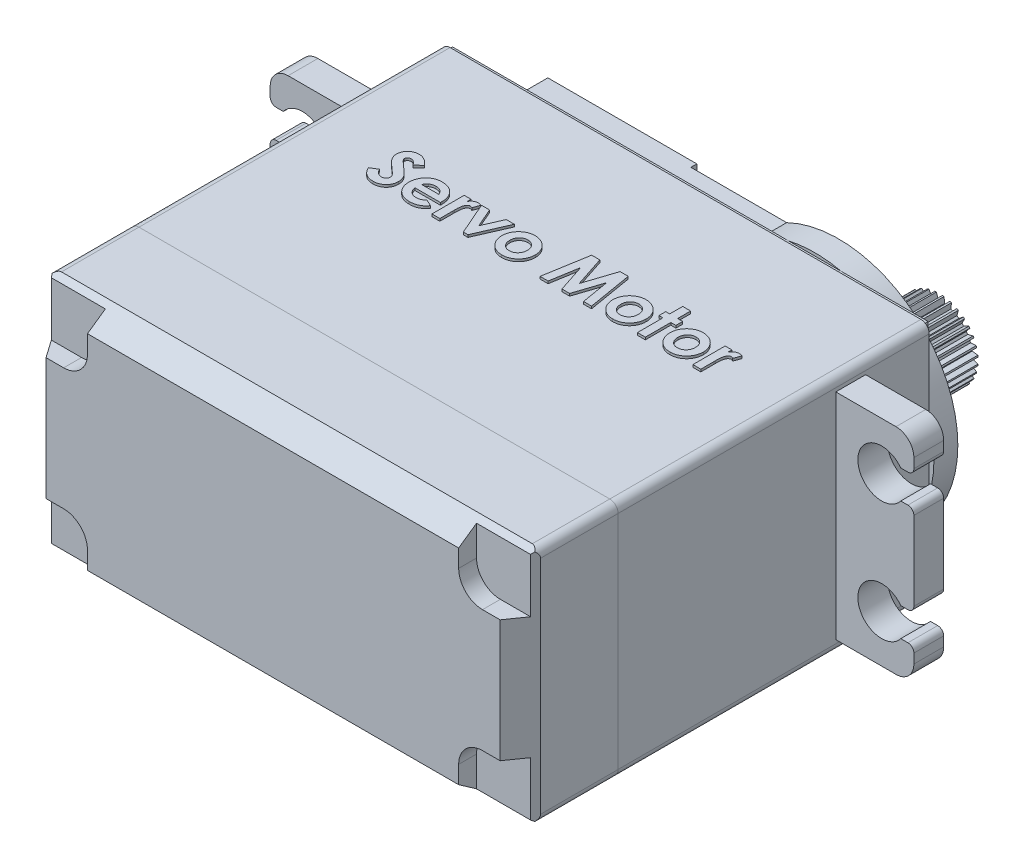
SolidWorks part; units mm, degrees
ref_plane "Front Plane" through (0, 0, 0) normal (0, 0, 1) x (1, 0, 0)
ref_plane "Top Plane" through (0, 0, 0) normal (0, 1, 0) x (1, 0, 0)
ref_plane "Right Plane" through (0, 0, 0) normal (1, 0, 0) x (0, 0, -1)
sketch "Sketch1" plane through (0, 0, 0) normal (0, 0, 1) x (1, 0, 0)
  line L1 (20.45, 10) -> (-20.45, 10)
  line L2 (20.45, 10) -> (20.45, -10)
  line L3 (20.45, -10) -> (-20.45, -10)
  line L4 (-20.45, 10) -> (-20.45, -10)
  line L5 (20.45, 10) -> (-20.45, -10) construction
  line L6 (20.45, -10) -> (-20.45, 10) construction
  point P0 (0, 0)
  dimension "D1" = 20
  dimension "D2" = 40.9
extrude "Boss-Extrude1" add sketch "Sketch1" along normal blind 19.3
sketch "Sketch2" plane through (0, 0, 0) normal (0, 0, -1) x (-1, 0, 0)
  line L4 (20.45, -10) -> (20.45, 10)
  line L5 (20.45, 10) -> (-20.45, 10)
  line L6 (-20.45, 10) -> (-20.45, -10)
  line L7 (-20.45, -10) -> (20.45, -10)
  line L8 (20.45, -10) -> (20.45, 10)
  line L9 (20.45, 10) -> (-20.45, 10)
  line L10 (-20.45, 10) -> (-20.45, -10)
  line L11 (-20.45, -10) -> (20.45, -10)
  dimension "D1" = 0
extrude "Boss-Extrude2" add sketch "Sketch2" along normal blind 6.8 separate body
sketch "Sketch3" plane through (0, 0, 19.3) normal (0, 0, 1) x (1, 0, 0)
  line L4 (-20.45, 10) -> (-20.45, -10)
  line L5 (-20.45, -10) -> (20.45, -10)
  line L6 (20.45, -10) -> (20.45, 10)
  line L7 (20.45, 10) -> (-20.45, 10)
  line L8 (-20.45, 10) -> (-20.45, -10)
  line L9 (-20.45, -10) -> (20.45, -10)
  line L10 (20.45, -10) -> (20.45, 10)
  line L11 (20.45, 10) -> (-20.45, 10)
  dimension "D1" = 0
extrude "Boss-Extrude3" add sketch "Sketch3" along normal blind 8.5 separate body
chamfer "Chamfer1" distance 2 angle 35 4 edges at (20.45, 0, 27.8) (0, -10, 27.8) (-20.45, 0, 27.8) (0, 10, 27.8) first distance on face at (20.45, 0, 23.55) first distance on face at (0, -10, 23.55) first distance on face at (-20.45, 0, 23.55) first distance on face at (0, 10, 23.55)
sketch "Sketch4" plane through (0, 0, 27.8) normal (0, 0, 1) x (1, 0, 0)
  line L0 (0, 0) -> (0, 10) construction
  line L1 (-20.45, 10) -> (-15.57, 10)
  line L2 (-20.45, 10) -> (-20.45, 5.12)
  line L3 (-20.45, 5.12) -> (-17.57, 5.12)
  line L4 (-15.57, 10) -> (-15.57, 7.12)
  line L5 (-20.45, 10) -> (20.45, 10) construction
  line L6 (0, 0) -> (20.45, 0) construction
  line L7 (20.45, 10) -> (20.45, -10) construction
  line L8 (15.57, 10) -> (15.57, 7.12)
  line L9 (20.45, 5.12) -> (17.57, 5.12)
  line L10 (20.45, 10) -> (20.45, 5.12)
  line L11 (20.45, 10) -> (15.57, 10)
  line L12 (-15.57, -10) -> (-15.57, -7.12)
  line L13 (-20.45, -5.12) -> (-17.57, -5.12)
  line L14 (-20.45, -10) -> (-20.45, -5.12)
  line L15 (-20.45, -10) -> (-15.57, -10)
  line L16 (20.45, -10) -> (15.57, -10)
  line L17 (20.45, -10) -> (20.45, -5.12)
  line L18 (20.45, -5.12) -> (17.57, -5.12)
  line L19 (15.57, -10) -> (15.57, -7.12)
  arc A0 (-17.57, 5.12) -> (-15.57, 7.12) centre (-17.57, 7.12) ccw
  arc A1 (17.57, 5.12) -> (15.57, 7.12) centre (17.57, 7.12) cw
  arc A2 (-17.57, -5.12) -> (-15.57, -7.12) centre (-17.57, -7.12) cw
  arc A3 (17.57, -5.12) -> (15.57, -7.12) centre (17.57, -7.12) ccw
  dimension "D3" = 2
  dimension "D1" = 4.88
  dimension "D2" = 4.88
extrude "Cut-Extrude1" cut sketch "Sketch4" against normal blind 1.5
sketch "Sketch5" plane through (0, 0, -6.8) normal (0, 0, -1) x (-1, 0, 0)
  line L1 (19.95, 9.75) -> (-19.95, 9.75)
  line L2 (19.95, 9.75) -> (19.95, -9.75)
  line L3 (19.95, -9.75) -> (-19.95, -9.75)
  line L4 (-19.95, 9.75) -> (-19.95, -9.75)
  line L5 (19.95, 9.75) -> (-19.95, -9.75) construction
  line L6 (19.95, -9.75) -> (-19.95, 9.75) construction
  line L7 (20.45, 10) -> (-20.45, 10) construction
  line L8 (20.45, -10) -> (20.45, 10) construction
  point P0 (0, 0)
  dimension "D1" = 0.25
  dimension "D2" = 0.5
extrude "Boss-Extrude4" add sketch "Sketch5" along normal blind 0.4
sketch "Sketch7" plane through (0, 0, -7.2) normal (0, 0, -1) x (-1, 0, 0)
  line L0 (-20.45, 0) -> (20.45, 0) construction
  line L1 (-20.45, 10) -> (-20.45, -10) construction
  line L2 (20.45, -10) -> (20.45, 10) construction
  line L3 (20.45, 10) -> (-20.45, 10) construction
  line L4 (-6.09, 9.75) -> (-6.09, -9.75) construction
  line L5 (19.95, 9.75) -> (-19.95, 9.75) construction
  line L6 (-19.95, -9.75) -> (19.95, -9.75) construction
  line L7 (-6.09, 8.9995) -> (14.45, 8.9995)
  line L8 (14.45, 8.9995) -> (14.45, 3.9188)
  line L9 (14.45, -8.9995) -> (14.45, -3.9188)
  line L10 (-6.09, -8.9995) -> (14.45, -8.9995)
  arc A0 (-6.09, 8.9995) -> (-6.09, -8.9995) centre (-10.45, 0) ccw
  arc A1 (14.45, -3.9188) -> (14.45, 3.9188) centre (13.3905, 0) ccw
  point P23 (17.45, 0)
  dimension "D1" = 14.36
  dimension "D2" = 6
  dimension "D3" = 3
extrude "Boss-Extrude5" add sketch "Sketch7" along normal blind 2
sketch "Sketch8" plane through (0, 0, -9.2) normal (0, 0, -1) x (-1, 0, 0)
  circle A0 centre (-11.9002, 0) radius 6.5
  dimension "D1" = 13
extrude "Boss-Extrude6" add sketch "Sketch8" along normal blind 1.5
sketch "Sketch9" plane through (0, 0, -10.7) normal (0, 0, -1) x (-1, 0, 0)
  circle A0 centre (-11.9002, 0) radius 5.5
  dimension "D1" = 11
extrude "Boss-Extrude7" add sketch "Sketch9" along normal blind 0.5
sketch "Sketch10" plane through (0, 0, -11.2) normal (0, 0, -1) x (-1, 0, 0)
  circle A0 centre (-11.9002, 0) radius 3.25
  dimension "D1" = 6.5
extrude "Boss-Extrude8" add sketch "Sketch10" along normal blind 5
sketch "Sketch11" plane through (0, 0, -9.2) normal (0, 0, -1) x (-1, 0, 0)
  line L0 (-6.09, -8.9995) -> (14.45, -8.9995) construction
  line L1 (14.45, 8.9995) -> (1.95, 8.9995)
  line L2 (14.45, 8.9995) -> (14.45, -8.9995)
  line L3 (14.45, -8.9995) -> (1.95, -8.9995)
  line L4 (1.95, 8.9995) -> (1.95, 1.75)
  line L5 (13.45, 7.9995) -> (2.95, 7.9995)
  line L6 (2.95, 7.9995) -> (2.95, -7.9995)
  line L7 (13.45, -7.9995) -> (2.95, -7.9995)
  line L8 (13.45, 7.9995) -> (13.45, -7.9995)
  line L9 (1.95, -1.75) -> (1.95, -8.9995)
  line L10 (1.95, 8.9995) -> (1.95, -8.9995) construction
  arc A0 (1.95, 1.75) -> (1.95, -1.75) centre (1.95, 0) ccw
  dimension "D3" = 3.5
  dimension "D1" = 12.5
  dimension "D2" = 1
extrude "Boss-Extrude9" add sketch "Sketch11" along normal blind 0.5
fillet "Fillet1" radius 0.7 4 edges at (-20.45, -10, 9.65) (-20.45, 10, 9.65) (20.45, 10, 9.65) (20.45, -10, 9.65)
fillet "Fillet2" radius 0.7 4 edges at (20.45, 10, -3.4) (-20.45, 10, -3.4) (-20.45, -10, -3.4) (20.45, -10, -3.4)
fillet "Fillet3" radius 0.7 4 edges at (-20.45, 10, 22.55) (-20.45, -10, 22.55) (20.45, 10, 22.55) (20.45, -10, 22.55)
sketch "Sketch12" plane through (0, 0, -7.2) normal (0, 0, -1) x (-1, 0, 0)
  line L0 (20.45, 9) -> (25.5, 9)
  line L1 (20.45, -9.3) -> (20.45, 9.3) construction
  line L2 (0, 0) -> (30.9499, 0) construction
  line L3 (27, 7.5) -> (27, 6.7)
  line L4 (19.75, 10) -> (-19.75, 10) construction
  line L5 (0, 8.9995) -> (0, -8.9995) construction
  line L6 (1.95, 8.9995) -> (-6.09, 8.9995) construction
  line L7 (-6.09, -8.9995) -> (1.95, -8.9995) construction
  line L8 (25.9, 9) -> (25.9, 0) construction
  line L9 (25.9, 6.2) -> (26.5, 6.2)
  line L10 (25.9, 3.8) -> (26.5, 3.8)
  line L11 (27, 3.3) -> (27, -3.3)
  line L12 (25.9, -3.8) -> (26.5, -3.8)
  line L13 (25.9, -6.2) -> (26.5, -6.2)
  line L14 (27, -7.5) -> (27, -6.7)
  line L15 (20.45, -9) -> (25.5, -9)
  line L16 (20.45, 9) -> (20.45, -9)
  arc A0 (25.9, 6.2) -> (25.9, 3.8) centre (24.3, 5) ccw
  arc A1 (26.5, 3.8) -> (27, 3.3) centre (26.5, 3.3) cw
  arc A2 (26.5, 6.2) -> (27, 6.7) centre (26.5, 6.7) ccw
  arc A3 (25.5, 9) -> (27, 7.5) centre (25.5, 7.5) cw
  arc A4 (25.5, -9) -> (27, -7.5) centre (25.5, -7.5) ccw
  arc A5 (26.5, -6.2) -> (27, -6.7) centre (26.5, -6.7) cw
  arc A6 (26.5, -3.8) -> (27, -3.3) centre (26.5, -3.3) ccw
  arc A7 (25.9, -6.2) -> (25.9, -3.8) centre (24.3, -5) cw
  point P25 (27, 3.8)
  point P42 (27, 0)
  point P43 (27, -3.8)
  dimension "D3" = 4
  dimension "D7" = 0.5
  dimension "D8" = 1.5
  dimension "D1" = 6.55
  dimension "D2" = 1
  dimension "D4" = 5
  dimension "D5" = 24.3
  dimension "D6" = 1.1
extrude "Boss-Extrude10" add sketch "Sketch12" against normal blind 2.5 from offset 5.74 offset against normal yes
mirror "Mirror1" about plane through (0, 0, 0) normal (1, 0, 0) of "Boss-Extrude10"
sketch "Sketch13" plane through (0, -10, 0) normal (0, -1, 0) x (1, 0, 0)
  line L0 (-19.75, 6.25) -> (20.45, 6.25) construction
  line L1 (-19.75, 19.3) -> (-19.75, -6.8) construction
  line L2 (20.45, 19.3) -> (20.45, -6.8) construction
  text T0 "Servo Motor" font "Century Gothic" height in points 14
extrude "Boss-Extrude11" add sketch "Sketch13" against normal blind 0.2 from surface starting at face at (0, 10, 6.25)
sketch "Sketch14" plane through (0, -10, 0) normal (0, -1, 0) x (1, 0, 0)
  line L0 (-19.75, 6.25) -> (20.45, 6.25) construction
  line L1 (-19.75, 19.3) -> (-19.75, -6.8) construction
  line L2 (20.45, 19.3) -> (20.45, -6.8) construction
  text T0 "Servo Motor" font "Century Gothic" height in points 14
extrude "Boss-Extrude12" add sketch "Sketch14" along normal blind 0.2
sketch "Sketch15" plane through (0, 0, -16.2) normal (0, 0, -1) x (-1, 0, 0)
  line L0 (-11.9002, 0) -> (-11.9002, 3.25) construction
  line L1 (-11.8002, 2.7882) -> (-11.6502, 3.2404)
  line L2 (-12.0002, 2.7882) -> (-12.1502, 3.2404)
  arc A0 (-11.8002, 2.7882) -> (-12.0002, 2.7882) centre (-11.9002, 0) ccw
  circle A1 centre (-11.9002, 0) radius 3.25 construction
  arc A2 (-11.6502, 3.2404) -> (-12.1502, 3.2404) centre (-11.9002, 0) ccw
  dimension "D1" = 5.58
  dimension "D2" = 0.25
  dimension "D3" = 0.1
extrude "Cut-Extrude2" cut sketch "Sketch15" against normal up to surface (5 mm away) up to face at (8.6502, 0, -11.2)
pattern_circular "CirPattern3" count 32 over 360 about axis through (11.9002, 0, -16.2) along (0, 0, -1) of "Cut-Extrude2"
